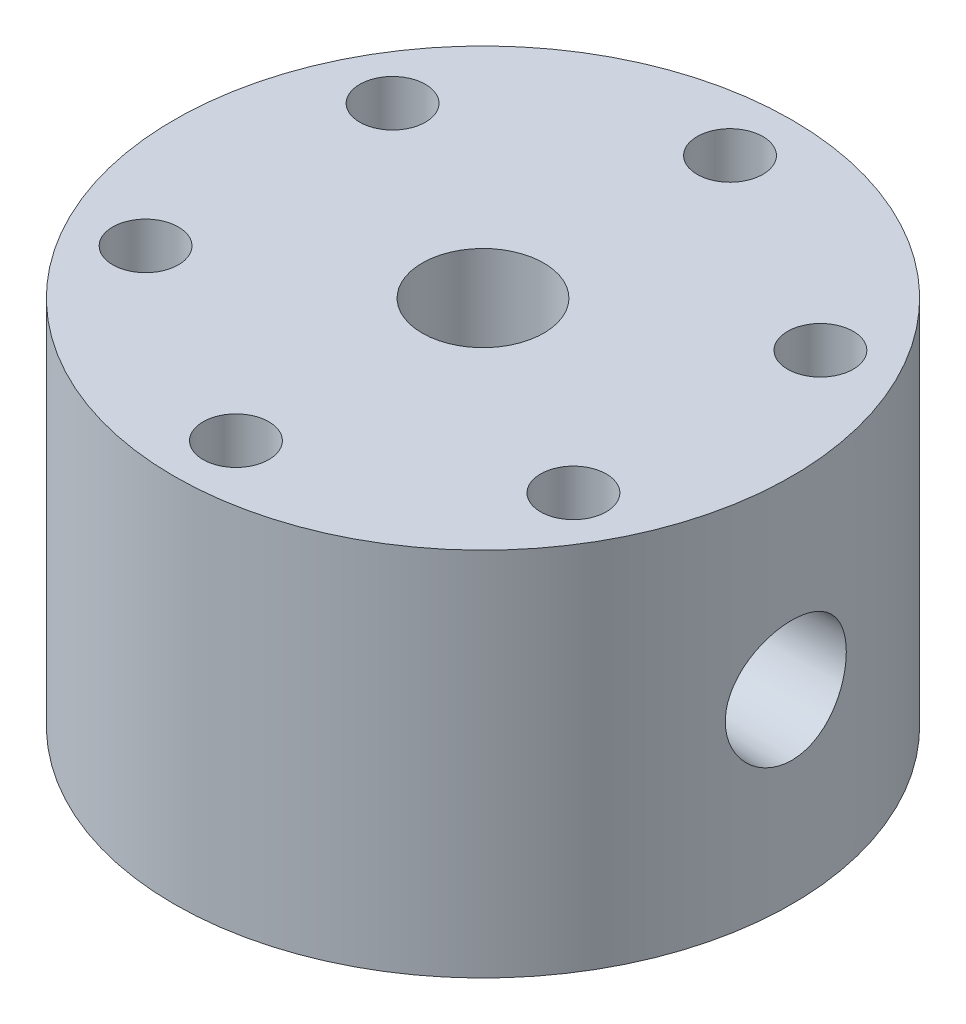
SolidWorks part; units mm, degrees
ref_plane "Front Plane" through (0, 0, 0) normal (0, 0, 1) x (1, 0, 0)
ref_plane "Top Plane" through (0, 0, 0) normal (0, 1, 0) x (1, 0, 0)
ref_plane "Right Plane" through (0, 0, 0) normal (1, 0, 0) x (0, 0, -1)
sketch "Sketch1" plane through (0, 0, 0) normal (0, 0, 1) x (1, 0, 0)
  line L2 (-20.6375, 0) -> (-31.75, 0)
  line L3 (-31.75, 0) -> (-31.75, 38.1)
  line L4 (-31.75, 38.1) -> (-3.556, 38.1)
  line L6 (-3.556, 38.1) -> (-3.556, 6.35)
  line L10 (0, 0) -> (0, 15.7692) construction
  line L12 (-4.7625, 6.35) -> (-11.1125, 0)
  line L13 (-3.556, 6.35) -> (-4.7625, 6.35)
  line L14 (-11.1125, 0) -> (-17.5895, 0)
  line L15 (-17.5895, 0) -> (-17.5895, 2.032)
  line L17 (-17.5895, 2.032) -> (-20.6375, 2.032)
  line L18 (-20.6375, 2.032) -> (-20.6375, 0)
  dimension "D1" = 3.556
  dimension "D2" = 6.35
  dimension "D3" = 135
  dimension "D4" = 38.1
  dimension "D5" = 31.75
  dimension "D6" = 11.1125
  dimension "D7" = 3.048
  dimension "D8" = 2.032
  dimension "D9" = 20.6375
revolve "Revolve1" add sketch "Sketch1" angle 360 about L10
hole_wizard "M14x1.5 Tapped Hole1" positions "Sketch2" profile "Sketch4" tap size "M14x1.5" standard "ANSI Metric"
sketch "Sketch2" plane through (0, 38.1, 0) normal (0, 1, 0) x (1, 0, 0)
  point P0 (0, 0)
sketch "Sketch4" plane through (0, 38.1, 0) normal (1, 0, 0) x (0, 0, 1)
  line L0 (0, 0) -> (0, 29.1554)
  line L1 (0, 29.1554) -> (6.25, 25.4)
  line L2 (6.25, 25.4) -> (6.25, 0)
  line L5 (6.25, 0) -> (0, 0)
  line L10 (0, 29.1554) -> (-6.25, 25.4) construction
  line L11 (0, -6.35) -> (0, 107.95) construction
  dimension "Tap Drill Dia." = 12.5
  dimension "Tap Drill Depth" = 25.4
  dimension "Drill Angle" = 118
cosmetic thread "Hole Thread3"
ref_plane "Plane1" through (31.75, 0, 0) normal (1, 0, 0) x (0, 0, -1)
ref_plane "Plane2" through (-31.75, 0, 0) normal (-1, 0, 0) x (0, 0, 1)
hole_wizard "1/4 NPT Tapped Hole1" positions "Sketch5" profile "Sketch6" size "1/4" standard "ANSI Inch"
sketch "Sketch5" plane through (31.75, 0, 0) normal (1, 0, 0) x (0, 0, -1)
  line L0 (31.75, 38.1) -> (-31.75, 38.1) construction
  point P0 (0, 19.05)
  dimension "D1" = 19.05
sketch "Sketch6" plane through (31.75, 19.05, 0) normal (0, 1, 0) x (0, 0, -1)
  line L0 (0, 0) -> (0, 20.3603)
  line L1 (5.5626, 17.018) -> (0, 20.3603)
  line L2 (-5.5626, 17.018) -> (0, 20.3603) construction
  line L3 (5.5626, 17.018) -> (5.5626, 9.906)
  line L4 (5.5626, 9.906) -> (5.9437, 9.906)
  line L5 (5.9437, 9.906) -> (6.2403, 0)
  line L6 (-5.9437, 9.906) -> (-6.2403, 0) construction
  line L7 (6.2403, 0) -> (0, 0)
  line L8 (0, -6.35) -> (0, 107.95) construction
  line L11 (-5.5626, 9.906) -> (-5.9437, 9.906) construction
  dimension "Tap Drill Dia." = 11.1252
  dimension "Tap Drill Depth" = 17.018
  dimension "Thread Dia." = 12.4806
  dimension "Thread Angle" = 3.43
  dimension "Thread Depth" = 9.906
  dimension "Drill Angle" = 118
cosmetic thread "Hole Thread1"
hole_wizard "1/4 NPT Tapped Hole2" positions "Sketch7" profile "Sketch8" size "1/4" standard "ANSI Inch"
sketch "Sketch7" plane through (-31.75, 0, 0) normal (-1, 0, 0) x (0, 0, 1)
  line L0 (31.75, 38.1) -> (-31.75, 38.1) construction
  point P0 (0, 19.05)
  dimension "D1" = 19.05
sketch "Sketch8" plane through (-31.75, 19.05, 0) normal (0, 1, 0) x (0, 0, 1)
  line L0 (0, 0) -> (0, 20.3603)
  line L1 (5.5626, 17.018) -> (0, 20.3603)
  line L2 (-5.5626, 17.018) -> (0, 20.3603) construction
  line L3 (5.5626, 17.018) -> (5.5626, 9.906)
  line L4 (5.5626, 9.906) -> (5.9437, 9.906)
  line L5 (5.9437, 9.906) -> (6.2403, 0)
  line L6 (-5.9437, 9.906) -> (-6.2403, 0) construction
  line L7 (6.2403, 0) -> (0, 0)
  line L8 (0, -6.35) -> (0, 107.95) construction
  line L11 (-5.5626, 9.906) -> (-5.9437, 9.906) construction
  dimension "Tap Drill Dia." = 11.1252
  dimension "Tap Drill Depth" = 17.018
  dimension "Thread Dia." = 12.4806
  dimension "Thread Angle" = 3.43
  dimension "Thread Depth" = 9.906
  dimension "Drill Angle" = 118
cosmetic thread "Hole Thread2" parameters "D1"=9.906, "D2"=13.7086
hole_wizard "1/16 (0.0625) Diameter Hole1" positions "Sketch9" profile "Sketch10" hole size "1/16" standard "ANSI Inch"
sketch "Sketch9" plane through (31.75, 0, 0) normal (1, 0, 0) x (0, 0, -1)
  point P0 (0, 19.05)
sketch "Sketch10" plane through (31.75, 19.05, 0) normal (0, 1, 0) x (0, 0, -1)
  line L0 (0, 0) -> (0, 29.0519)
  line L1 (0, 29.0519) -> (0.7937, 28.575)
  line L2 (0.7937, 28.575) -> (0.7937, 0)
  line L5 (0.7937, 0) -> (0, 0)
  line L10 (0, 29.0519) -> (-0.7938, 28.575) construction
  line L11 (0, -6.35) -> (0, 107.95) construction
  dimension "Hole Dia." = 1.5875
  dimension "Hole Depth" = 28.575
  dimension "Drill Angle" = 118
hole_wizard "3/32 (0.09375) Diameter Hole1" positions "Sketch11" profile "Sketch12" hole size "3/32" standard "ANSI Inch"
sketch "Sketch11" plane through (-31.75, 0, 0) normal (-1, 0, 0) x (0, 0, 1)
  point P0 (0, 19.05)
sketch "Sketch12" plane through (-31.75, 19.05, 0) normal (0, 1, 0) x (0, 0, 1)
  line L0 (0, 0) -> (0, 29.4174)
  line L1 (0, 29.4174) -> (1.1906, 28.702)
  line L2 (1.1906, 28.702) -> (1.1906, 0)
  line L5 (1.1906, 0) -> (0, 0)
  line L10 (0, 29.4174) -> (-1.1906, 28.702) construction
  line L11 (0, -6.35) -> (0, 107.95) construction
  dimension "Hole Dia." = 2.3812
  dimension "Hole Depth" = 28.702
  dimension "Drill Angle" = 118
hole_wizard "1/4 Clearance Hole1" positions "Sketch15" profile "Sketch16" hole size "1/4" standard "ANSI Inch" end condition through all
sketch "Sketch15" plane through (0, 38.1, 0) normal (0, 1, 0) x (1, 0, 0)
  line L0 (0, 0) -> (16.0984, 0) construction
  line L2 (0, 0) -> (21.997, 12.7) construction
  point P0 (21.997, 12.7)
  dimension "D1" = 25.4
  dimension "D2" = 30
sketch "Sketch16" plane through (21.997, 38.1, -12.7) normal (1, 0, 0) x (0, 0, 1)
  line L0 (0, 0) -> (0, 38.1)
  line L1 (0, 38.1) -> (3.3782, 38.1)
  line L2 (3.3782, 38.1) -> (3.3782, 0)
  line L5 (3.3782, 0) -> (0, 0)
  line L11 (0, -6.35) -> (0, 107.95) construction
  dimension "Thru Hole Dia." = 6.7564
  dimension "Thru Hole Depth" = 38.1
pattern_circular "CirPattern1" count 6 over 360 about axis through (0, 0, 0) along (0, -1, 0) of "1/4 Clearance Hole1"
ref_plane "Plane3" through (15.875, 0, -27.4963) normal (0.5, 0, -0.866) x (0, -1, 0)
hole_wizard "1/4 NPT Tapped Hole3" positions "Sketch17" profile "Sketch18" size "1/4" standard "ANSI Inch"
sketch "Sketch17" plane through (15.875, 0, -27.4963) normal (0.5, 0, -0.866) x (0, -1, 0)
  point P0 (-19.05, 0)
  point P3 (-19.05, 0)
  dimension "D1" = 19.05
sketch "Sketch18" plane through (15.875, 19.05, -27.4963) normal (0, 1, 0) x (-0.866, 0, -0.5)
  line L0 (0, 0) -> (0, 20.3603)
  line L1 (5.5626, 17.018) -> (0, 20.3603)
  line L2 (-5.5626, 17.018) -> (0, 20.3603) construction
  line L3 (5.5626, 17.018) -> (5.5626, 9.906)
  line L4 (5.5626, 9.906) -> (5.9437, 9.906)
  line L5 (5.9437, 9.906) -> (6.2403, 0)
  line L6 (-5.9437, 9.906) -> (-6.2403, 0) construction
  line L7 (6.2403, 0) -> (0, 0)
  line L8 (0, -6.35) -> (0, 107.95) construction
  line L11 (-5.5626, 9.906) -> (-5.9437, 9.906) construction
  dimension "Tap Drill Dia." = 11.1252
  dimension "Tap Drill Depth" = 17.018
  dimension "Thread Dia." = 12.4806
  dimension "Thread Angle" = 3.43
  dimension "Thread Depth" = 9.906
  dimension "Drill Angle" = 118
cosmetic thread "Hole Thread5"
hole_wizard "1/32 (0.03125) Diameter Hole1" positions "Sketch21" profile "Sketch22" hole size "1/32" standard "ANSI Inch"
sketch "Sketch21" plane through (15.875, 0, -27.4963) normal (0.5, 0, -0.866) x (0, -1, 0)
  point P0 (-19.05, 0)
sketch "Sketch22" plane through (15.875, 19.05, -27.4963) normal (0, 1, 0) x (-0.866, 0, -0.5)
  line L0 (0, 0) -> (0, 28.8135)
  line L1 (0, 28.8135) -> (0.3969, 28.575)
  line L2 (0.3969, 28.575) -> (0.3969, 0)
  line L5 (0.3969, 0) -> (0, 0)
  line L10 (0, 28.8135) -> (-0.3969, 28.575) construction
  line L11 (0, -6.35) -> (0, 107.95) construction
  dimension "Hole Dia." = 0.7937
  dimension "Hole Depth" = 28.575
  dimension "Drill Angle" = 118
ref_axis "Axis1" through (0, 0, -34.925) along (0, 0, 1)
ref_plane "Plane4" through (0, 0, 0) normal (-0.7071, 0.7071, 0) x (0, 0, 1)
hole_wizard "1/8 (0.125) Diameter Hole1" positions "Sketch25" profile "Sketch24" hole size "1/8" standard "ANSI Inch"
sketch "Sketch25" plane through (0, 0, 0) normal (-0.7071, 0.7071, 0) x (0, 0, 1)
  line L0 (0, 0) -> (0, -7.8577) construction
  ellipse E0 centre (0, 0) end of major axis (-11.1125, 0) minor radius 7.8577 construction
  point P0 (0, -3.175)
  point P14 (0, -6.2686)
  point P15 (0, -6.3794)
  dimension "D1" = 3.175
sketch "Sketch24" plane through (-2.2451, -2.2451, 0) normal (0, 0, 1) x (0.7071, 0.7071, 0)
  line L0 (0, 0) -> (0, 26.3539)
  line L1 (0, 26.3539) -> (1.5875, 25.4)
  line L2 (1.5875, 25.4) -> (1.5875, 0)
  line L5 (1.5875, 0) -> (0, 0)
  line L10 (0, 26.3539) -> (-1.5875, 25.4) construction
  line L11 (0, -6.35) -> (0, 107.95) construction
  dimension "Hole Dia." = 3.175
  dimension "Hole Depth" = 25.4
  dimension "Drill Angle" = 118
